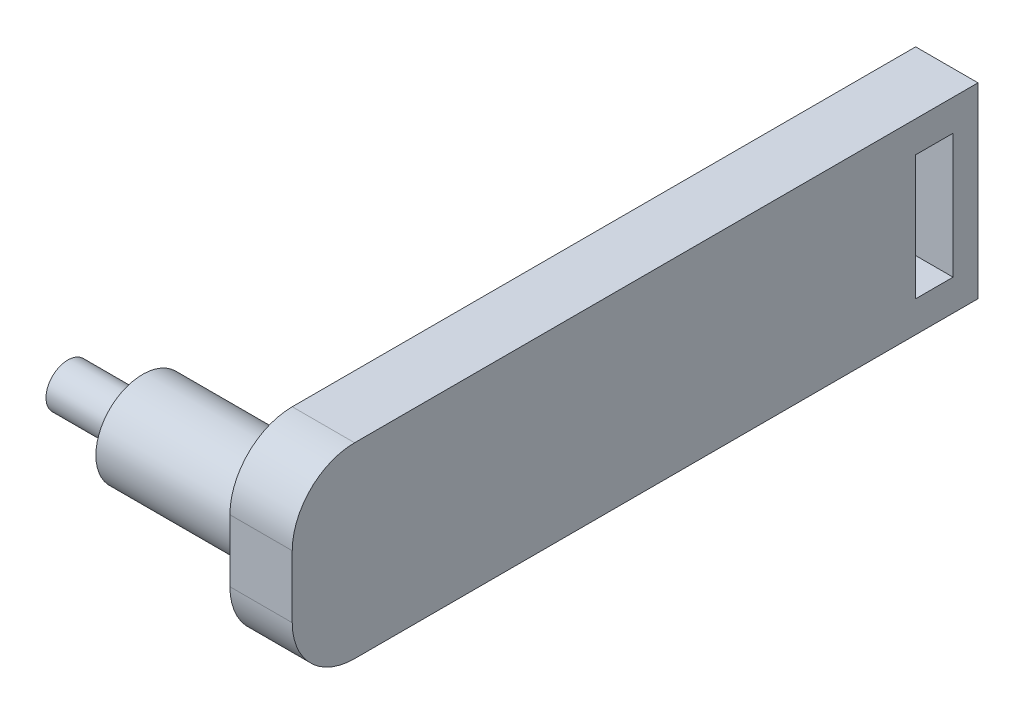
SolidWorks part; units mm, degrees
ref_plane "Front Plane" through (0, 0, 0) normal (0, 0, 1) x (1, 0, 0)
ref_plane "Top Plane" through (0, 0, 0) normal (0, 1, 0) x (1, 0, 0)
ref_plane "Right Plane" through (0, 0, 0) normal (1, 0, 0) x (0, 0, -1)
sketch "Sketch1" plane through (0, 0, 0) normal (0, 1, 0) x (1, 0, 0)
  line L1 (-61.8805, -26.2097) -> (-56.8805, -26.2097)
  line L2 (-61.8805, -26.2097) -> (-61.8805, 28.7903)
  line L3 (-61.8805, 28.7903) -> (-56.8805, 28.7903)
  line L4 (-56.8805, -26.2097) -> (-56.8805, 28.7903)
  line L6 (-56.8805, 28.7903) -> (-56.8805, 23.7903)
  dimension "D5" = 5
extrude "Boss-Extrude1" add sketch "Sketch1" along normal blind 15 contours L1 L4 L3 L2 region at (-59.3805, 0, -1.2903)
sketch "Sketch2" plane through (-61.8805, 0, 0) normal (-1, 0, 0) x (0, 0, 1)
  line L2 (26.2097, 0) -> (-28.7903, 0) construction
  line L3 (-28.7903, 15) -> (-28.7903, 0) construction
  line L5 (-26.7903, 2.5) -> (-23.7903, 2.5)
  line L6 (-26.7903, 2.5) -> (-26.7903, 12.5)
  line L7 (-26.7903, 12.5) -> (-23.7903, 12.5)
  line L8 (-23.7903, 2.5) -> (-23.7903, 12.5)
  dimension "D4" = 2.5
  dimension "D5" = 10
  dimension "D6" = 2
  dimension "D7" = 3
fillet "Fillet1" radius 5 2 edges at (-59.3805, 15, 26.2097) (-59.3805, 0, 26.2097)
sketch "Sketch3" plane through (-61.8805, 0, 0) normal (-1, 0, 0) x (0, 0, 1)
  line L3 (21.2097, 15) -> (-28.7903, 15) construction
  line L4 (26.2097, 10) -> (26.2097, 5) construction
  circle A1 centre (21.2097, 7.5) radius 3.75
  dimension "D1" = 7.5
  dimension "D2" = 5
  dimension "D3" = 7.5
extrude "Cut-Extrude1" cut sketch "Sketch2" against normal up to surface (5 mm away) up to face at (-56.8805, 7.5, 6.5549)
extrude "Boss-Extrude2" add sketch "Sketch3" along normal blind 12
sketch "Sketch4" plane through (-73.8805, 0, 0) normal (-1, 0, 0) x (0, 0, 1)
  circle A0 centre (21.2097, 7.5) radius 2.9
  circle A1 centre (21.2097, 7.5) radius 1.75
extrude "Boss-Extrude3" add sketch "Sketch4" along normal blind 6 contours A1
